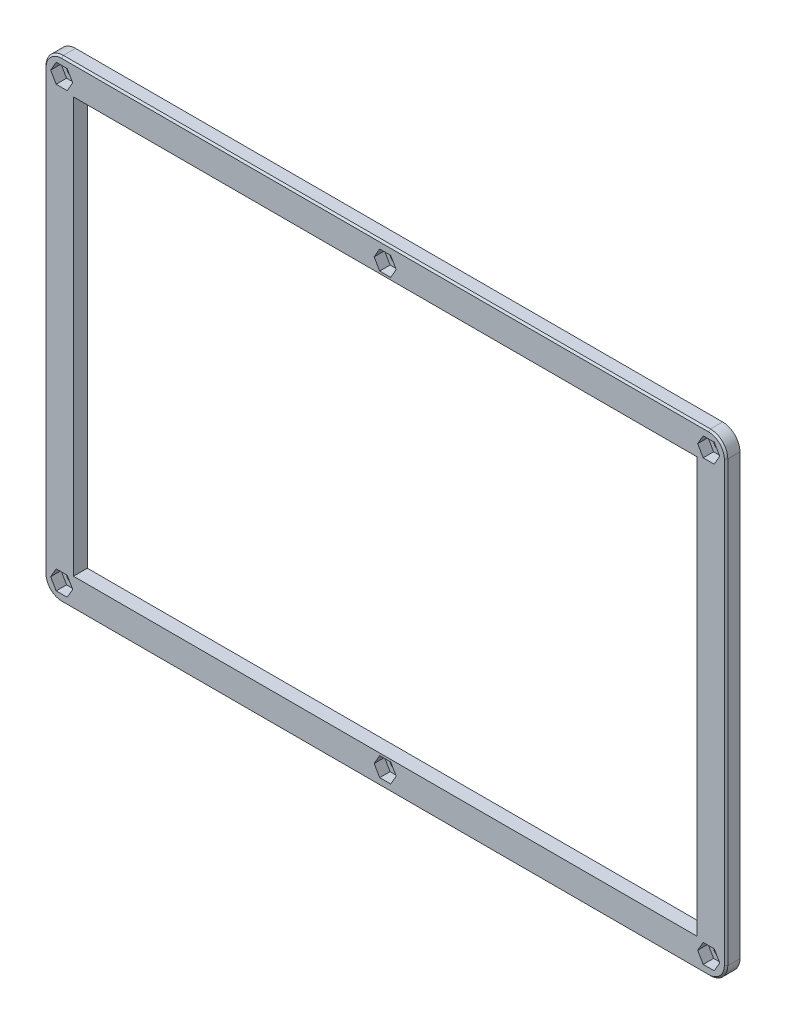
SolidWorks part; units mm, degrees
ref_plane "Alzado" through (0, 0, 0) normal (0, 0, 1) x (1, 0, 0)
ref_plane "Planta" through (0, 0, 0) normal (0, 1, 0) x (1, 0, 0)
ref_plane "Vista lateral" through (0, 0, 0) normal (1, 0, 0) x (0, 0, -1)
sketch "Croquis1" plane through (0, 0, 0) normal (0, 0, 1) x (1, 0, 0)
  line L1 (-89.8, 59.8) -> (89.8, 59.8)
  line L2 (-89.8, 59.8) -> (-89.8, -59.8)
  line L3 (-89.8, -59.8) -> (89.8, -59.8)
  line L4 (89.8, 59.8) -> (89.8, -59.8)
  line L5 (-89.8, 59.8) -> (89.8, -59.8) construction
  line L6 (-89.8, -59.8) -> (89.8, 59.8) construction
  line L7 (-88.2, 58.2) -> (88.2, 58.2)
  line L8 (-88.2, 58.2) -> (-88.2, -58.2)
  line L9 (-88.2, -58.2) -> (88.2, -58.2)
  line L10 (88.2, 58.2) -> (88.2, -58.2)
  line L11 (-88.2, 58.2) -> (88.2, -58.2) construction
  line L12 (-88.2, -58.2) -> (88.2, 58.2) construction
  point P0 (0, 0)
  point P6 (0, 0)
  dimension "D1" = 179.6
  dimension "D2" = 119.6
  dimension "D3" = 1.6
  dimension "D4" = 1.6
extrude "Saliente-Extruir1" add sketch "Croquis1" along normal blind 40
sketch "Croquis2" plane through (0, 0, 0) normal (0, 0, -1) x (-1, 0, 0)
  line L1 (-98.2, 68.2) -> (98.2, 68.2)
  line L2 (-98.2, 68.2) -> (-98.2, -68.2)
  line L3 (-98.2, -68.2) -> (98.2, -68.2)
  line L4 (98.2, 68.2) -> (98.2, -68.2)
  line L5 (-98.2, 68.2) -> (98.2, -68.2) construction
  line L6 (-98.2, -68.2) -> (98.2, 68.2) construction
  line L7 (-88.2, 58.2) -> (88.2, 58.2)
  line L8 (-88.2, 58.2) -> (-88.2, -58.2)
  line L9 (-88.2, -58.2) -> (88.2, -58.2)
  line L10 (88.2, 58.2) -> (88.2, -58.2)
  line L11 (-88.2, 58.2) -> (88.2, -58.2) construction
  line L12 (-88.2, -58.2) -> (88.2, 58.2) construction
  point P1 (0, 0)
  point P6 (0, 0)
  dimension "D1" = 10
  dimension "D2" = 10
extrude "Saliente-Extruir2" add sketch "Croquis2" along normal blind 4
sketch "Croquis10" plane through (0, 0, 40) normal (0, 0, 1) x (1, 0, 0)
  line L1 (89.8, 59.8) -> (-89.8, 59.8)
  line L2 (89.8, 59.8) -> (89.8, -59.8)
  line L3 (89.8, -59.8) -> (-89.8, -59.8)
  line L4 (-89.8, 59.8) -> (-89.8, -59.8)
  line L5 (89.8, 59.8) -> (-89.8, -59.8) construction
  line L6 (89.8, -59.8) -> (-89.8, 59.8) construction
  point P0 (0, 0)
extrude "Cortar-Extruir6" cut sketch "Croquis10" against normal through all
sketch "Croquis7" plane through (0, 0, -4) normal (0, 0, -1) x (-1, 0, 0)
  line L0 (0, 0) -> (0, 50000) construction
  line L1 (0, 0) -> (50000, 0) construction
  line L2 (0, 63.2) -> (50000, 63.2) construction
  line L3 (93.2, 64.2122) -> (93.2, -49935.7878) construction
  line L4 (98.2, 68.2) -> (-98.2, 68.2) construction
  line L5 (98.2, -68.2) -> (98.2, 68.2) construction
  circle A0 centre (0, 63.2) radius 1.6
  circle A2 centre (93.2, 63.2) radius 1.6
  circle A3 centre (93.2, 0) radius 1.6 construction
  circle A4 centre (50, 63.2) radius 1.6 construction
  circle A5 centre (-50, 63.2) radius 1.6 construction
  circle A6 centre (-93.2, 63.2) radius 1.6
  circle A7 centre (-93.2, 0) radius 1.6 construction
  circle A8 centre (-93.2, -63.2) radius 1.6
  circle A9 centre (-50, -63.2) radius 1.6 construction
  circle A10 centre (50, -63.2) radius 1.6 construction
  circle A11 centre (93.2, -63.2) radius 1.6
  circle A12 centre (0, -63.2) radius 1.6
  dimension "D3" = 3.2
  dimension "D1" = 5
  dimension "D2" = 5
  dimension "D4" = 100
extrude "Cortar-Extruir3" cut sketch "Croquis7" against normal through all
sketch "Croquis9" plane through (0, 0, -4) normal (0, 0, -1) x (-1, 0, 0)
  line L1 (-90.0246, 63.2) -> (-91.6123, 65.95)
  line L2 (-91.6123, 65.95) -> (-94.7877, 65.95)
  line L3 (-94.7877, 65.95) -> (-96.3754, 63.2)
  line L4 (-96.3754, 63.2) -> (-94.7877, 60.45)
  line L5 (-94.7877, 60.45) -> (-91.6123, 60.45)
  line L6 (-91.6123, 60.45) -> (-90.0246, 63.2)
  line L7 (3.1754, 63.2) -> (1.5877, 65.95)
  line L8 (1.5877, 65.95) -> (-1.5877, 65.95)
  line L9 (-1.5877, 65.95) -> (-3.1754, 63.2)
  line L10 (-3.1754, 63.2) -> (-1.5877, 60.45)
  line L11 (-1.5877, 60.45) -> (1.5877, 60.45)
  line L12 (1.5877, 60.45) -> (3.1754, 63.2)
  line L13 (3.1754, -63.2) -> (1.5877, -60.45)
  line L14 (1.5877, -60.45) -> (-1.5877, -60.45)
  line L15 (-1.5877, -60.45) -> (-3.1754, -63.2)
  line L16 (-3.1754, -63.2) -> (-1.5877, -65.95)
  line L17 (-1.5877, -65.95) -> (1.5877, -65.95)
  line L18 (1.5877, -65.95) -> (3.1754, -63.2)
  line L19 (-90.0246, -63.2) -> (-91.6123, -60.45)
  line L20 (-91.6123, -60.45) -> (-94.7877, -60.45)
  line L21 (-94.7877, -60.45) -> (-96.3754, -63.2)
  line L22 (-96.3754, -63.2) -> (-94.7877, -65.95)
  line L23 (-94.7877, -65.95) -> (-91.6123, -65.95)
  line L24 (-91.6123, -65.95) -> (-90.0246, -63.2)
  line L25 (96.3754, -63.2) -> (94.7877, -60.45)
  line L26 (94.7877, -60.45) -> (91.6123, -60.45)
  line L27 (91.6123, -60.45) -> (90.0246, -63.2)
  line L28 (90.0246, -63.2) -> (91.6123, -65.95)
  line L29 (91.6123, -65.95) -> (94.7877, -65.95)
  line L30 (94.7877, -65.95) -> (96.3754, -63.2)
  line L31 (96.3754, 63.2) -> (94.7877, 65.95)
  line L32 (94.7877, 65.95) -> (91.6123, 65.95)
  line L33 (91.6123, 65.95) -> (90.0246, 63.2)
  line L34 (90.0246, 63.2) -> (91.6123, 60.45)
  line L35 (91.6123, 60.45) -> (94.7877, 60.45)
  line L36 (94.7877, 60.45) -> (96.3754, 63.2)
  circle A0 centre (-93.2, 63.2) radius 2.75 construction
  circle A1 centre (0, 63.2) radius 2.75 construction
  circle A2 centre (0, -63.2) radius 2.75 construction
  circle A3 centre (-93.2, -63.2) radius 2.75 construction
  circle A4 centre (93.2, -63.2) radius 2.75 construction
  circle A5 centre (93.2, 63.2) radius 2.75 construction
  dimension "D1" = 5.5
extrude "Cortar-Extruir5" cut sketch "Croquis9" against normal through all from offset 1 offset against normal yes
fillet "Redondeo1" radius 5 4 edges at (98.2, 68.2, -2) (98.2, -68.2, -2) (-98.2, -68.2, -2) (-98.2, 68.2, -2)
chamfer "Chaflán2" distance 0.5 angle 45 8 edges at (96.7355, -66.7355, 0) (0, -68.2, 0) (-96.7355, -66.7355, 0) (-98.2, 0, 0) (-96.7355, 66.7355, 0) (0, 68.2, 0) (96.7355, 66.7355, 0) (98.2, 0, 0)
chamfer "Chaflán3" distance 1 angle 45 6 edges at (94.8, 63.2, -4) (-1.6, 63.2, -4) (91.6, -63.2, -4) (1.6, -63.2, -4) (-91.6, -63.2, -4) (-94.8, 63.2, -4)
